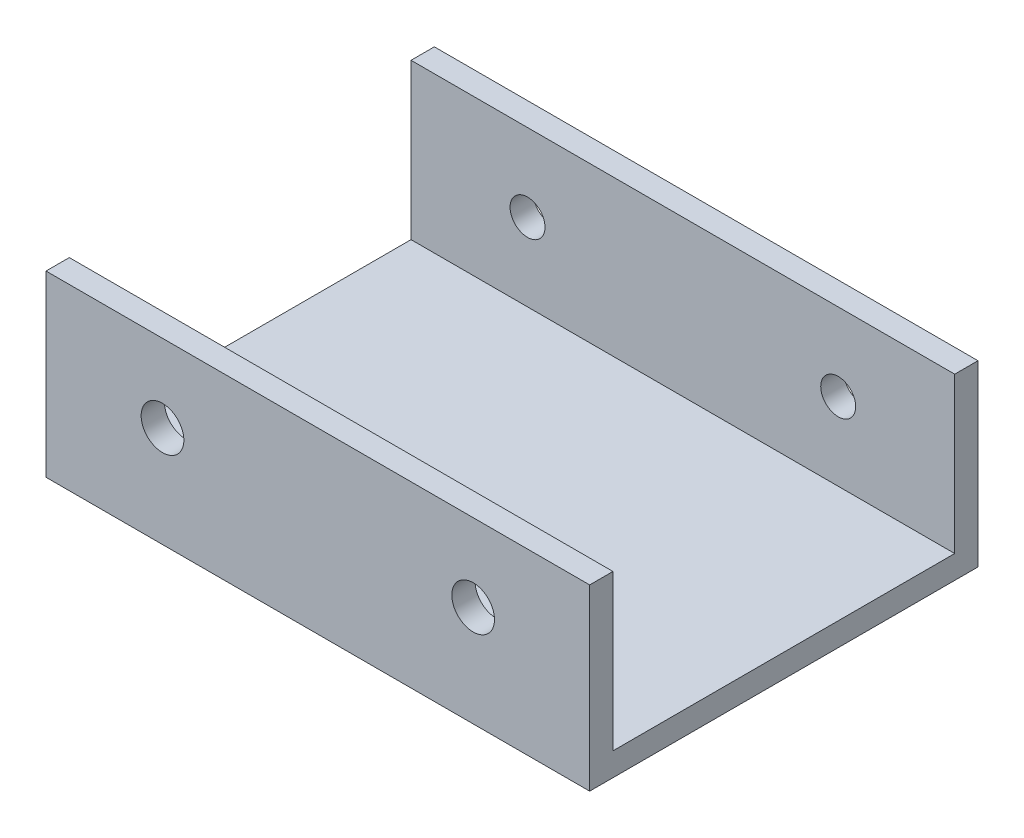
SolidWorks part; units mm, degrees
ref_plane "Front Plane" through (0, 0, 0) normal (0, 0, 1) x (1, 0, 0)
ref_plane "Top Plane" through (0, 0, 0) normal (0, 1, 0) x (1, 0, 0)
ref_plane "Right Plane" through (0, 0, 0) normal (1, 0, 0) x (0, 0, -1)
sketch "Sketch1" plane through (0, 0, 0) normal (0, 0, 1) x (1, 0, 0)
  line L0 (35, 20) -> (35, 0) construction
  line L1 (0, 0) -> (70, 0)
  line L2 (0, 0) -> (0, 20)
  line L3 (0, 20) -> (70, 20)
  line L4 (70, 0) -> (70, 20)
  line L5 (0, 10) -> (70, 10) construction
  circle A0 centre (15, 10) radius 2.25
  circle A1 centre (55, 10) radius 2.25
  dimension "D3" = 4.5
  dimension "D4" = 40
  dimension "D1" = 20
  dimension "D2" = 70
extrude "Boss-Extrude1" add sketch "Sketch1" along normal blind 3
sketch "Sketch2" plane through (0, 0, 0) normal (0, -1, 0) x (1, 0, 0)
  line L0 (70, 3) -> (70, 0) construction
  line L1 (0, 0) -> (70, 0)
  line L2 (0, 0) -> (0, 50)
  line L3 (0, 50) -> (70, 50)
  line L4 (70, 0) -> (70, 50)
  dimension "D1" = 50
extrude "Boss-Extrude2" add sketch "Sketch2" along normal blind 3
sketch "Sketch3" plane through (0, 0, 50) normal (0, 0, 1) x (1, 0, 0)
  line L0 (70, -3) -> (70, 0) construction
  line L1 (0, 0) -> (70, 0)
  line L2 (0, 0) -> (0, 20)
  line L3 (0, 20) -> (70, 20)
  line L4 (70, 0) -> (70, 20)
  line L5 (35, 20) -> (35, 0) construction
  line L6 (0, 10) -> (70, 10) construction
  circle A0 centre (15, 10) radius 2.75
  circle A1 centre (55, 10) radius 2.75
  point P16 (0, 0)
  point P17 (11.8887, 10)
  dimension "D2" = 5.5
  dimension "D1" = 20
  dimension "D3" = 40
extrude "Boss-Extrude3" add sketch "Sketch3" against normal blind 3
